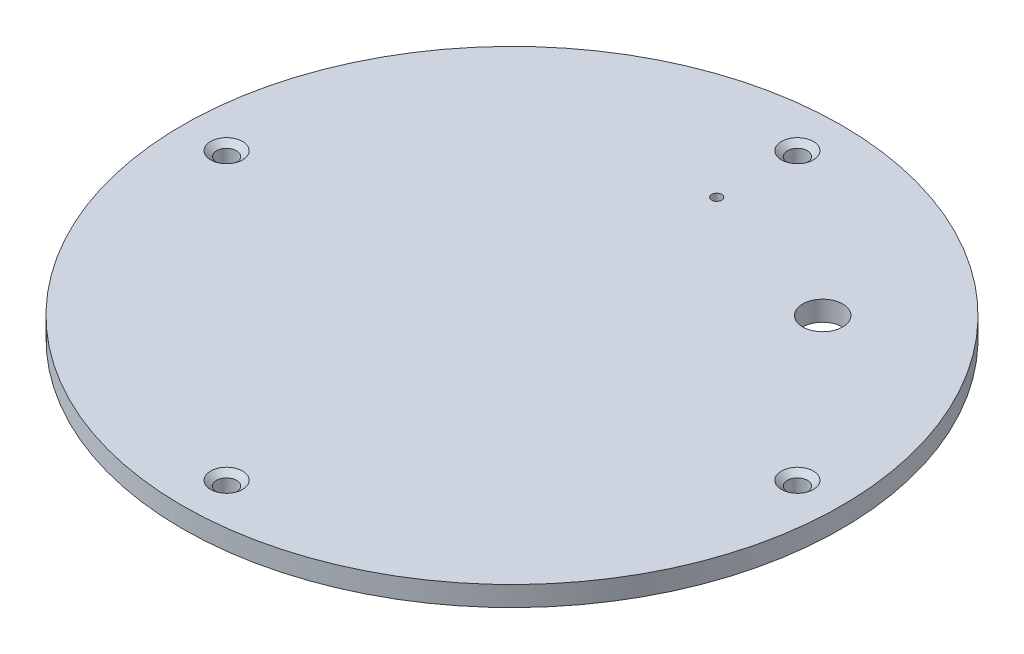
SolidWorks part; units mm, degrees
material "1060 Alloy"
ref_plane "Front Plane" through (0, 0, 0) normal (0, 0, 1) x (1, 0, 0)
ref_plane "Top Plane" through (0, 0, 0) normal (0, 1, 0) x (1, 0, 0)
ref_plane "Right Plane" through (0, 0, 0) normal (1, 0, 0) x (0, 0, -1)
sketch "Sketch1" plane through (0, 0, 0) normal (0, 1, 0) x (1, 0, 0)
  circle A0 centre (0, 0) radius 16.5
  dimension "D1" = 33
extrude "Boss-Extrude1" add sketch "Sketch1" along normal blind 1
sketch "Sketch6" plane through (0, 1, 0) normal (0, 1, 0) x (1, 0, 0)
  line L0 (0, 0) -> (13.1331, 13.1331) construction
  line L1 (0, 0) -> (0, 10.25) construction
  circle A0 centre (0, 10.25) radius 0.25
  circle A1 centre (7.7782, 7.7782) radius 1
  dimension "D1" = 10.25
  dimension "D3" = 0.5
  dimension "D4" = 2
  dimension "D2" = 0
  dimension "D5" = 11
  dimension "D6" = 45
extrude "Cut-Extrude1" cut sketch "Sketch6" against normal through all both and the other way through all
hole_wizard "CSK for M2 Flat Head Machine Screw1" positions "Sketch13" profile "Sketch14" countersink size "M2" standard "ANSI Metric" end condition through all
sketch "Sketch13" plane through (0, 1, 0) normal (0, 1, 0) x (1, 0, 0)
  point P0 (0, 14.29)
  point P2 (-14.29, 0)
  point P4 (0, -14.29)
  point P6 (14.29, 0)
  dimension "D1" = 14.29
  dimension "D2" = 14.29
  dimension "D3" = 14.29
  dimension "D4" = 14.29
sketch "Sketch14" plane through (0, 1, -14.29) normal (1, 0, 0) x (0, 0, 1)
  line L0 (0, 0) -> (0, 1)
  line L1 (0, 1) -> (0.5, 1)
  line L2 (0.5, 1) -> (0.5, 0.2517)
  line L3 (0.5, 0.2517) -> (0.8, 0)
  line L5 (0.8, 0) -> (0, 0)
  line L6 (-0.5, 0.2517) -> (-0.8, 0) construction
  line L11 (0, -6.35) -> (0, 107.95) construction
  dimension "Thru Hole Dia." = 1
  dimension "Thru Hole Depth" = 1
  dimension "Near C'Sink Dia." = 1.6
  dimension "Near C'Sink Angle" = 100
